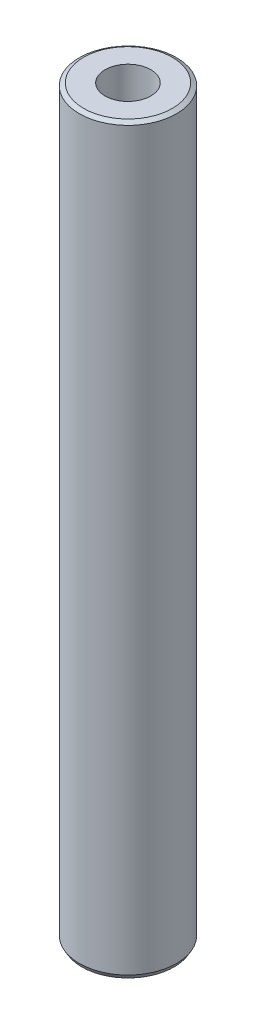
SolidWorks part; units mm, degrees
ref_plane "Front Plane" through (0, 0, 0) normal (0, 0, 1) x (1, 0, 0)
ref_plane "Top Plane" through (0, 0, 0) normal (0, 1, 0) x (1, 0, 0)
ref_plane "Right Plane" through (0, 0, 0) normal (1, 0, 0) x (0, 0, -1)
sketch "Sketch1" plane through (0, 0, 0) normal (0, 1, 0) x (1, 0, 0)
  circle A0 centre (0, 0) radius 7.5
  dimension "SHAFT_OD" = 15
extrude "Boss-Extrude1" add sketch "Sketch1" along normal blind 114.5859
sketch "Sketch2" plane through (0, 0, 0) normal (0, 1, 0) x (1, 0, 0)
  circle A0 centre (0, 0) radius 3.5249
  dimension "BORE_D" = 7.0498
extrude "Cut-Extrude1" cut sketch "Sketch2" along normal through all
chamfer "Chamfer1" distance 0.3811 angle 60 2 edges at (0, 114.5859, 7.5) (0, 0, 7.5) first distance on face at (0, 114.5859, 7.5) first distance on face at (0, 0, 3.5249)
